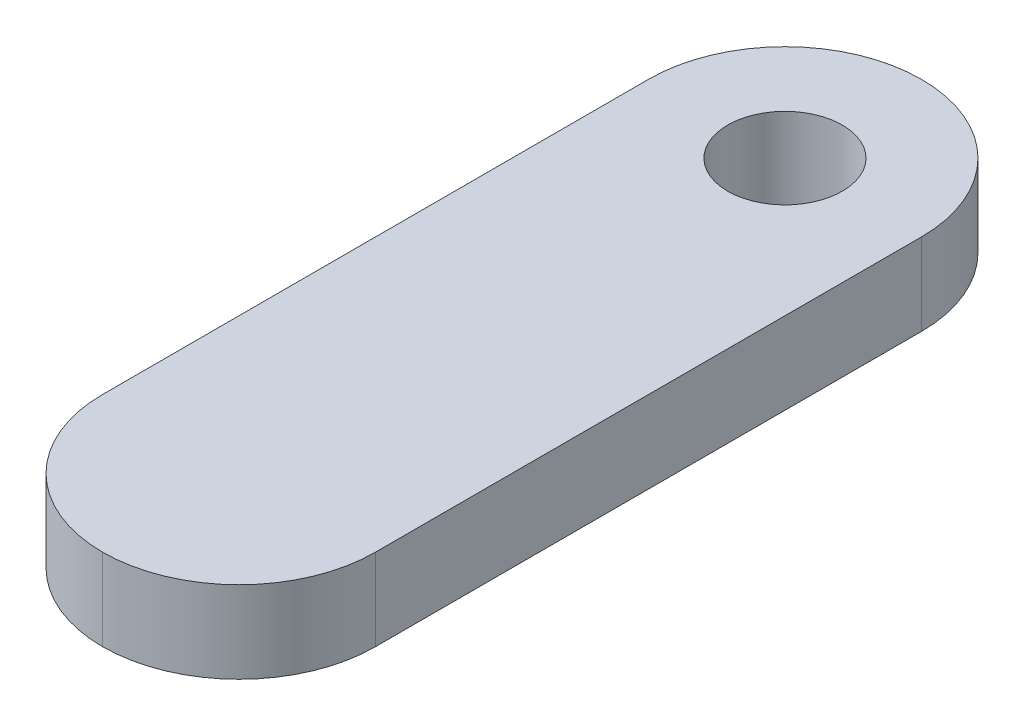
SolidWorks part; units mm, degrees
ref_plane "Alzado" through (0, 0, 0) normal (0, 0, 1) x (1, 0, 0)
ref_plane "Planta" through (0, 0, 0) normal (0, 1, 0) x (1, 0, 0)
ref_plane "Vista lateral" through (0, 0, 0) normal (1, 0, 0) x (0, 0, -1)
sketch "Croquis1" plane through (0, 0, 0) normal (0, 1, 0) x (1, 0, 0)
  line L1 (5, -15) -> (-5, -15)
  line L2 (5, -15) -> (5, 15)
  line L3 (5, 15) -> (-5, 15)
  line L4 (-5, -15) -> (-5, 15)
  line L5 (5, -15) -> (-5, 15) construction
  line L6 (5, 15) -> (-5, -15) construction
  point P0 (0, 0)
  dimension "D1" = 10
  dimension "D2" = 30
extrude "Saliente-Extruir1" add sketch "Croquis1" along normal mid plane 3
fillet "Redondeo1" radius 5 2 edges at (5, 0, -15) (-5, 0, -15)
sketch "Croquis2" plane through (0, 1.5, 0) normal (0, 1, 0) x (1, 0, 0)
  circle A0 centre (0, 10) radius 2.1
  dimension "D1" = 4.2
extrude "Cortar-Extruir1" cut sketch "Croquis2" against normal blind 3.5
sketch "Croquis3" plane through (0, -1.5, 0) normal (0, -1, 0) x (1, 0, 0)
  line L0 (5, 15) -> (5, -10) construction
  line L1 (-5, 15) -> (5, 15)
  line L2 (-5, 15) -> (-5, 3)
  line L3 (-5, 3) -> (5, 3)
  line L4 (5, 15) -> (5, 3)
  dimension "D1" = 12
extrude "Cortar-Extruir2" [suppressed] cut sketch "Croquis3" against normal blind 1.5
fillet "Redondeo2" [suppressed] radius 2
fillet "Redondeo3" radius 5 2 edges at (-5, 0, 15) (5, 0, 15)
